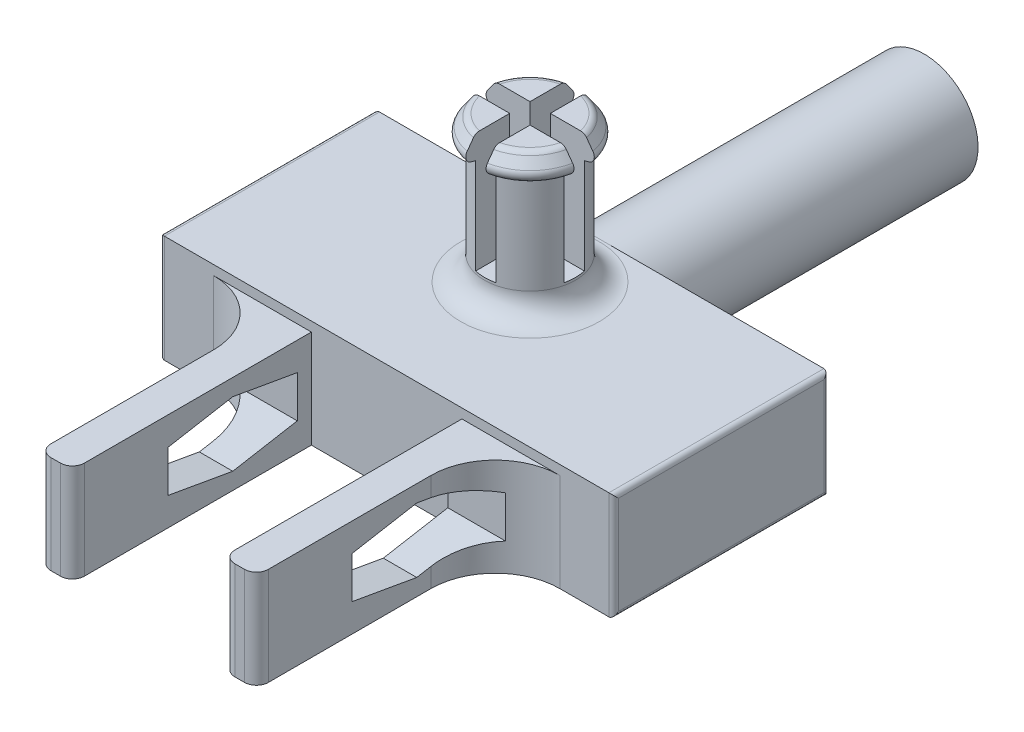
SolidWorks part; units mm, degrees
ref_plane "Front Plane" through (0, 0, 0) normal (0, 0, 1) x (1, 0, 0)
ref_plane "Top Plane" through (0, 0, 0) normal (0, 1, 0) x (1, 0, 0)
ref_plane "Right Plane" through (0, 0, 0) normal (1, 0, 0) x (0, 0, -1)
sketch "Szkic1" plane through (0, 0, 0) normal (0, 1, 0) x (1, 0, 0)
  line L0 (0, -13.1707) -> (0, 4.5) construction
  line L1 (4.55, -4.5) -> (-4.55, -4.5)
  line L2 (9.5, -4.5) -> (9.5, 4.5)
  line L3 (9.5, 4.5) -> (-9.5, 4.5)
  line L4 (-9.5, -4.5) -> (-9.5, 4.5)
  line L5 (9.5, -4.5) -> (-9.5, 4.5) construction
  line L6 (9.5, 4.5) -> (-9.5, -4.5) construction
  line L7 (-9.5, -4.5) -> (-4.55, -4.5)
  line L10 (2.5793, 4.5) -> (-2.5793, 4.5)
  line L13 (-4.55, -4.5) -> (-7.25, -4.5)
  line L14 (-4.55, -4.5) -> (-3.15, -4.5)
  line L15 (-4.55, -4.5) -> (-4.55, -14.5)
  line L16 (-4.55, -14.5) -> (-3.15, -14.5)
  line L17 (-3.15, -4.5) -> (-3.15, -14.5)
  line L18 (4.55, -4.5) -> (3.15, -4.5)
  line L19 (4.55, -4.5) -> (4.55, -14.5)
  line L20 (4.55, -14.5) -> (3.15, -14.5)
  line L21 (3.15, -4.5) -> (3.15, -14.5)
  line L22 (4.55, -4.5) -> (9.5, -4.5)
  line L23 (-4.55, -4.5) -> (-4.55, -7.2)
  line L26 (4.55, -4.5) -> (7.25, -4.5)
  line L27 (4.55, -4.5) -> (4.55, -7.2)
  arc A0 (-4.55, -7.2) -> (-7.25, -4.5) centre (-7.25, -7.2) ccw
  arc A1 (7.25, -4.5) -> (4.55, -7.2) centre (7.25, -7.2) ccw
  point P0 (0, 0)
  dimension "D1" = 9
  dimension "D2" = 19
  dimension "D3" = 10
  dimension "D4" = 1.4
  dimension "D5" = 6.3
  dimension "D6" = 2.7
extrude "Dodanie-wyciągnięcie1" add sketch "Szkic1" along normal blind 4.5 contours L1 L22 L2 L3 L4 L7 region at (0, 0, 0)
extrude "Dodanie-wyciągnięcie2" add sketch "Szkic1<7>" along normal blind 4.1 contours A0 L15 L7 | L17 L1 L15 L16 | A1 L22 L19 | L1 L21 L20 L19 region at (3.85, 0, 9.5) region at (5.1531, 0, 5.1031) region at (-3.85, 0, 9.5) region at (-5.1531, 0, 5.1031)
sketch "Szkic1<7>" plane through (0, 0, 0) normal (0, 1, 0) x (1, 0, 0) same geometry as "Szkic1"
ref_plane "Płaszczyzna1" through (0, 0, -4.5) normal (0, 0, -1) x (-1, 0, 0)
sketch "Szkic2" plane through (0, 0, -4.5) normal (0, 0, -1) x (-1, 0, 0)
  line L0 (0, 0) -> (0, 4.5) construction
  line L1 (-9.5, 4.5) -> (9.5, 4.5) construction
  circle A0 centre (0, 2.25) radius 2.25
  point P5 (0, 2.25)
  dimension "D1" = 4.5
extrude "Dodanie-wyciągnięcie3" add sketch "Szkic2" along normal blind 13.5
ref_plane "Płaszczyzna2" through (-3.15, 0, 0) normal (1, 0, 0) x (0, 0, -1)
sketch "Szkic3" plane through (-3.15, 0, 0) normal (1, 0, 0) x (0, 0, -1)
  line L0 (-7.79, 3.4) -> (-10.49, 2.9239)
  line L1 (-10.49, 2.9239) -> (-10.49, 1.1761)
  line L2 (-10.49, 1.1761) -> (-7.79, 0.7)
  line L3 (-7.79, 0.7) -> (-5.09, 1.1761)
  line L4 (-5.09, 1.1761) -> (-5.09, 2.9239)
  line L5 (-5.09, 2.9239) -> (-7.79, 3.4)
  line L7 (-4.5, 4.1) -> (-14.5, 4.1) construction
  line L8 (-4.5, 0) -> (-14.5, 0) construction
  dimension "D1" = 0.7
  dimension "D2" = 0.7
  dimension "D3" = 100
  dimension "D4" = 100
  dimension "D5" = 5.4
extrude "Wytnij-wyciągnięcie2" cut sketch "Szkic3" along normal through all both and the other way through all
fillet "Zaokrąglenie1" radius 0.5 4 edges at (3.15, 2.05, 14.5) (4.55, 2.05, 14.5) (-4.55, 2.05, 14.5) (-3.15, 2.05, 14.5)
fillet "Zaokrąglenie2" radius 0.2 8 edges at (-9.5, 2.25, -4.5) (-9.5, 4.5, 0) (9.5, 0, 0) (-9.5, 2.25, 4.5) (9.5, 2.25, 4.5) (9.5, 2.25, -4.5) (9.5, 4.5, 0) (-9.5, 0, 0)
ref_plane "Płaszczyzna3" through (0, 4.5, 0) normal (0, 1, 0) x (1, 0, 0)
sketch "Szkic4" plane through (0, 4.5, 0) normal (0, 1, 0) x (1, 0, 0)
  line L0 (-9.3, 1.5) -> (9.3, 1.5) construction
  line L1 (2.475, 4.5) -> (-2.475, 4.5) construction
  line L3 (-9.3, 4.5) -> (-9.3, -4.5) construction
  line L4 (9.3, -4.5) -> (9.3, 4.5) construction
  circle A0 centre (0, 1.5) radius 1.9
  point P6 (0, 1.5)
  dimension "D1" = 3.8
  dimension "D2" = 3
extrude "Dodanie-wyciągnięcie4" add sketch "Szkic4" along normal blind 5.1
ref_plane "Płaszczyzna4" through (0, 9.6, 0) normal (0, 1, 0) x (1, 0, 0)
sketch "Szkic5" plane through (0, 9.6, 0) normal (0, 1, 0) x (1, 0, 0)
  line L0 (0, 3.4) -> (0, -0.4) construction
  circle A0 centre (0, 1.5) radius 1.9 construction
  circle A1 centre (0, 1.5) radius 1.9
  point P5 (0, 1.5)
  dimension "D1" = 3.8
extrude "Dodanie-wyciągnięcie5" add sketch "Szkic5" along normal blind 1
fillet "Zaokrąglenie4" radius 1 1 edges at (0, 4.5, 0.4)
ref_axis "Oś1" through (0, 9.6, -1.5) along (0, -1, 0)
ref_point "Punkt1"
ref_point "Punkt2"
ref_plane "Płaszczyzna5" through (0, 0, 0) normal (1, 0, 0) x (0, 0, -1)
ref_plane "Płaszczyzna Dolnia" through (0, 0, 0) normal (0, -1, 0) x (-1, 0, 0)
ref_plane "Płaszczyzna6" through (0, 10.5, 0) normal (0, 1, 0) x (1, 0, 0)
sketch "Szkic7" plane through (0, 0, 0) normal (1, 0, 0) x (0, 0, -1)
  line L1 (3.4, 5.5) -> (3.4, 10.6) construction
  line L6 (3.4, 10.6) -> (3.4, 9.6)
  line L9 (3.4, 9.6) -> (4, 9.7608)
  line L10 (4, 9.7608) -> (3.4, 10.6)
  line L13 (1.5, 9.6) -> (1.5, 5.5) construction
  line L16 (4.95, 4.5) -> (-4.95, 4.5) construction
  point P2 (0, 0)
  point P3 (3.55, 9.6338)
  point P6 (3.4, 9.6)
  dimension "D1" = 2.5
  dimension "D2" = 75
  dimension "D4" = 5.1
ref_plane "Płaszczyzna7" through (0, 10.6, 0) normal (0, 1, 0) x (1, 0, 0)
revolve "Obrót1" add sketch "Szkic7" angle 360 about axis through (0, 9.6, -1.5) along (0, -1, 0)
fillet "Zaokrąglenie6" radius 0.3 2 edges at (0, 9.7608, 1) (0, 10.6, 0.4)
sketch "Szkic6" plane through (0, 10.6, 0) normal (0, 1, 0) x (1, 0, 0)
  line L0 (0.425, 4.7145) -> (0.425, 1.925)
  line L1 (-0.425, 4.7145) -> (-0.425, 1.925)
  line L2 (3.2145, 1.925) -> (0.425, 1.925)
  line L3 (3.2145, 1.075) -> (0.425, 1.075)
  line L4 (-0.425, 1.075) -> (-3.2145, 1.075)
  line L5 (-0.425, 1.925) -> (-3.2145, 1.925)
  line L6 (0.425, 1.075) -> (0.425, -1.7145)
  line L7 (-0.425, 1.075) -> (-0.425, -1.7145)
  line L8 (-0.425, 1.925) -> (0.425, 1.075) construction
  arc A4 (0.425, 4.7145) -> (-0.425, 4.7145) centre (0, 1.5) ccw
  arc A5 (3.2145, 1.075) -> (3.2145, 1.925) centre (0, 1.5) ccw
  arc A6 (-0.425, -1.7145) -> (0.425, -1.7145) centre (0, 1.5) ccw
  arc A7 (-3.2145, 1.925) -> (-3.2145, 1.075) centre (0, 1.5) ccw
  point P18 (0, 1.5)
  dimension "D1" = 0.85
  dimension "D2" = 0.85
extrude "Wytnij-wyciągnięcie3" cut sketch "Szkic6" against normal blind 5
